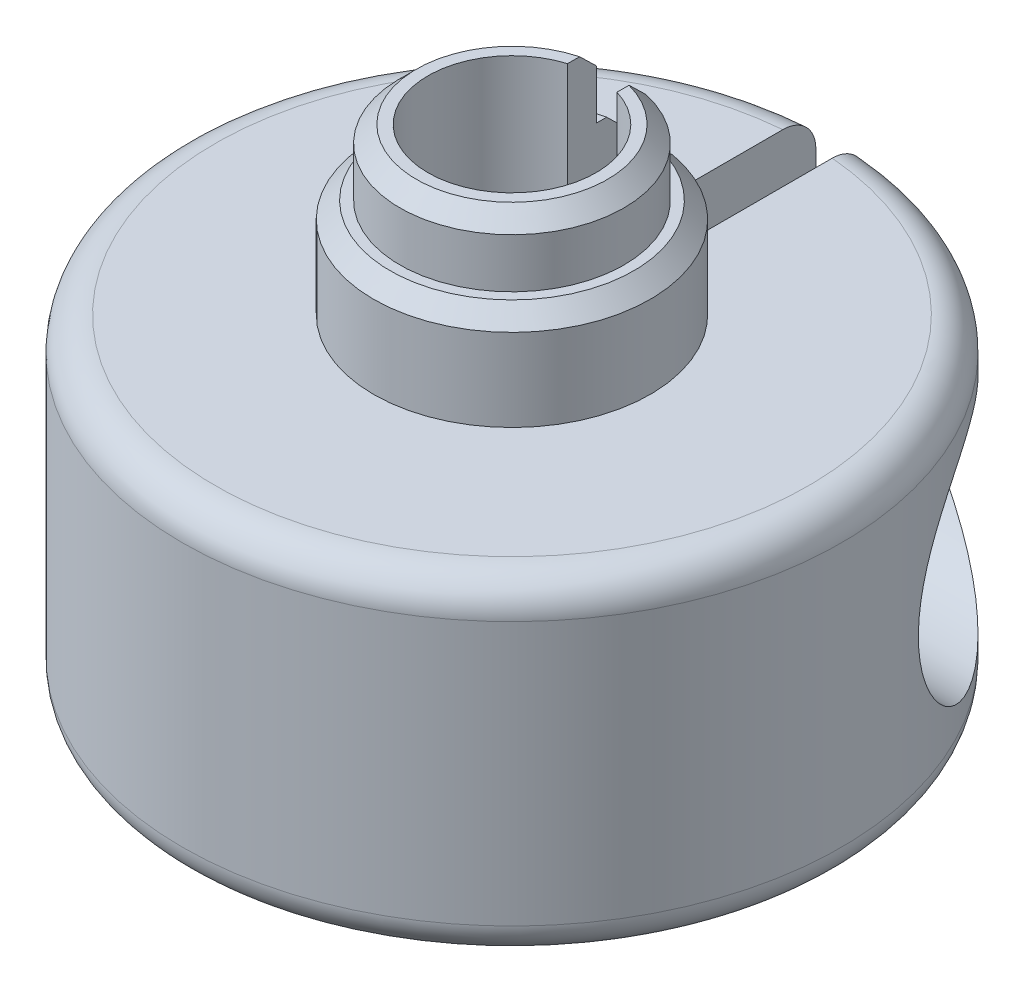
SolidWorks part; units mm, degrees
ref_plane "Front Plane" through (0, 0, 0) normal (0, 0, 1) x (1, 0, 0)
ref_plane "Top Plane" through (0, 0, 0) normal (0, 1, 0) x (1, 0, 0)
ref_plane "Right Plane" through (0, 0, 0) normal (1, 0, 0) x (0, 0, -1)
sketch "Sketch1" plane through (0, 0, 0) normal (0, 1, 0) x (1, 0, 0)
  circle A0 centre (0, 0) radius 4.05
  dimension "D1" = 8.1
extrude "Boss-Extrude1" add sketch "Sketch1" along normal blind 8
sketch "Sketch2" plane through (0, 8, 0) normal (0, 1, 0) x (1, 0, 0)
  circle A0 centre (0, 0) radius 10
  dimension "D1" = 20
extrude "Boss-Extrude2" add sketch "Sketch2" along normal blind 10
fillet "Fillet1" radius 1 3 edges at (0, 0, 4.05) (0, 8, 10) (0, 18, 10)
sketch "Sketch3" plane through (0, 18, 0) normal (0, 1, 0) x (1, 0, 0)
  circle A0 centre (0, 0) radius 2.55
  dimension "D1" = 5.1
extrude "Cut-Extrude1" cut sketch "Sketch3" against normal blind 10 contours A0
sketch "Sketch20" plane through (0, 18, 0) normal (0, 1, 0) x (1, 0, 0)
  line L1 (-0.75, 2.4372) -> (0.75, 2.4372)
  line L2 (-0.75, 2.4372) -> (-0.75, 9.9718)
  line L4 (0.75, 2.4372) -> (0.75, 9.9718)
  circle A0 centre (0, 0) radius 2.55 construction
  circle A1 centre (0, 0) radius 2.55 construction
  circle A2 centre (0, 0) radius 10 construction
  arc A3 (0.75, 9.9718) -> (-0.75, 9.9718) centre (0, 0) ccw
  dimension "D1" = 1.5
extrude "Cut-Extrude2" cut sketch "Sketch20" against normal up to surface (10 mm away) up to face at (0, 8, 9)
ref_plane "Plane2" through (10, 0, 0) normal (1, 0, 0) x (0, 0, -1)
hole_wizard "M2.5 Clearance Hole1" positions "Sketch32" profile "Sketch26" hole size "M2.5" standard "ANSI Metric" end condition through all
sketch "Sketch32" plane through (10, 0, 0) normal (1, 0, 0) x (0, 0, -1)
  line L0 (9.9718, 9) -> (9.9718, 17) construction
  line L1 (9.9718, 9) -> (9.9718, 17) construction
  line L2 (2.4372, 8) -> (2.4372, 18) construction
  line L3 (2.4372, 8) -> (2.4372, 18) construction
  line L4 (2.4372, 13) -> (9.9718, 13) construction
  point P0 (6.2045, 13)
  point P5 (9.9718, 13)
  point P17 (6.2045, 13)
sketch "Sketch26" plane through (10, 13, -6.2045) normal (0, 1, 0) x (0, 0, -1)
  line L0 (0, 0) -> (0, 20)
  line L1 (0, 20) -> (1.45, 20)
  line L2 (1.45, 20) -> (1.45, 0)
  line L5 (1.45, 0) -> (0, 0)
  line L11 (0, -6.35) -> (0, 107.95) construction
  dimension "Thru Hole Dia." = 2.9
  dimension "Thru Hole Depth" = 20
sketch "Sketch28" plane through (10, 0, 0) normal (1, 0, 0) x (0, 0, -1)
  circle A0 centre (6.2045, 13) radius 1.45 construction
  circle A1 centre (6.2045, 13) radius 1.45 construction
  circle A2 centre (6.2045, 13) radius 3.5
  dimension "D1" = 7
extrude "Cut-Extrude3" cut sketch "Sketch28" against normal blind 6.5
sketch "Sketch29" plane through (0, 0, 0) normal (0, 0, 1) x (1, 0, 0)
  line L0 (-4.05, 8) -> (-4.05, 1) construction
  line L1 (4.05, 8) -> (-4.05, 8)
  line L2 (4.05, 8) -> (4.05, 7.5)
  line L3 (4.05, 7.5) -> (-4.05, 7.5)
  line L4 (-4.05, 8) -> (-4.05, 7.5)
  dimension "D1" = 0.5
extrude "Cut-Extrude7" cut sketch "Sketch29" against normal through all
fillet "Fillet2" radius 0.25 3 edges at (3.3, 8, 0) (-3.3, 8, 0) (0, 7.5, 0)
sketch "Sketch30" plane through (0, 18, 0) normal (0, 1, 0) x (1, 0, 0)
  line L0 (-0.75, 8.9687) -> (-0.75, 2.4372) construction
  line L1 (0.75, 2.4372) -> (0.75, 8.9687) construction
  line L2 (-0.75, 3.3162) -> (-0.75, 2.4372)
  line L3 (0.75, 2.4372) -> (0.75, 3.3162)
  arc A0 (-0.75, 2.4372) -> (0.75, 2.4372) centre (0, 0) ccw
  arc A1 (-0.75, 3.3162) -> (0.75, 3.3162) centre (0, 0) ccw
  dimension "D1" = 3.4
extrude "Boss-Extrude3" add sketch "Sketch30" along normal blind 5
chamfer "Chamfer1" distance 0.5 angle 45 1 edges at (0, 23, 3.4)
ref_plane "Plane3" through (-10, 0, 0) normal (-1, 0, 0) x (0, 0, 1)
sketch "Sketch33" plane through (-10, 0, 0) normal (-1, 0, 0) x (0, 0, 1)
  line L0 (-3.3162, 18) -> (-8.9687, 18) construction
  line L1 (-3.1446, 13) -> (-4.6745, 15.65)
  line L2 (-4.6745, 15.65) -> (-7.7345, 15.65)
  line L3 (-7.7345, 15.65) -> (-9.2645, 13)
  line L4 (-9.2645, 13) -> (-7.7345, 10.35)
  line L5 (-7.7345, 10.35) -> (-4.6745, 10.35)
  line L6 (-4.6745, 10.35) -> (-3.1446, 13)
  circle A0 centre (-6.2045, 13) radius 2.65 construction
  dimension "D1" = 5.3
extrude "Cut-Extrude8" cut sketch "Sketch33" against normal blind 7
sketch "Sketch34" plane through (0, 23, 0) normal (0, 1, 0) x (1, 0, 0)
  line L0 (-0.75, 3.3162) -> (-0.75, 4.1325)
  line L1 (0.75, 3.3162) -> (0.75, 4.1325)
  line L2 (0.75, 3.3162) -> (0.75, 8.9687) construction
  arc A0 (-0.75, 4.1325) -> (0.75, 4.1325) centre (0, 0) ccw
  arc A1 (-0.75, 3.3162) -> (0.75, 3.3162) centre (0, 0) ccw
  dimension "D1" = 4.2
extrude "Boss-Extrude4" add sketch "Sketch34" along normal blind 3 from surface starting at face at (0, 18, 0.0288)
chamfer "Chamfer2" distance 0.5 angle 45 1 edges at (0, 21, 4.2)
sketch "Sketch35" plane through (0, 0, 0) normal (0, -1, 0) x (1, 0, 0)
  circle A0 centre (0, 0) radius 4.05
extrude "Cut-Extrude9" cut sketch "Sketch35" against normal up to surface (8 mm away) up to face at (0, 8, -0.2604)
equation "\"1.5.00mm\"=6"
